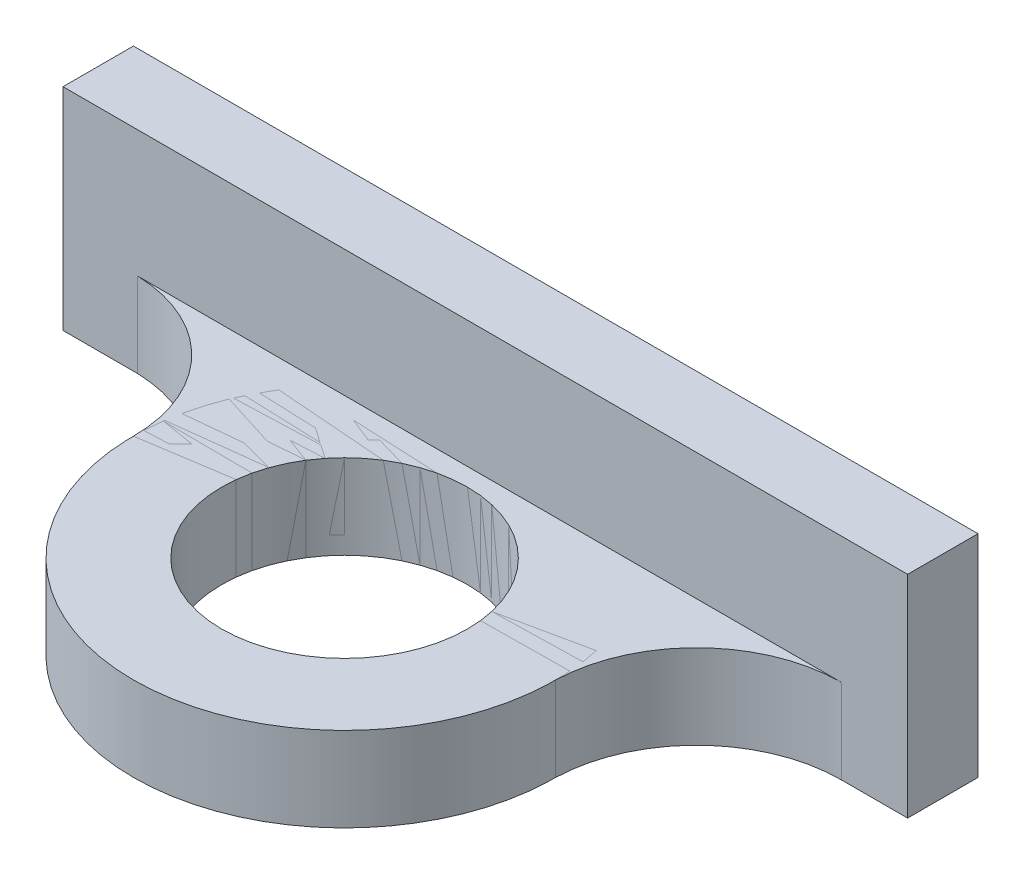
SolidWorks part; units mm, degrees
ref_plane "Front Plane" through (0, 0, 0) normal (0, 0, 1) x (1, 0, 0)
ref_plane "Top Plane" through (0, 0, 0) normal (0, 1, 0) x (1, 0, 0)
ref_plane "Right Plane" through (0, 0, 0) normal (1, 0, 0) x (0, 0, -1)
sketch "Sketch1" plane through (0, 0, 0) normal (0, 1, 0) x (1, 0, 0)
  circle A0 centre (0, 0) radius 17.4625
  circle A1 centre (0, 0) radius 30
  point P0 (0, 0)
  dimension "D2" = 34.925
  dimension "D1" = 60
extrude "Boss-Extrude1" add sketch "Sketch1" along normal blind 12
sketch "Sketch5" plane through (0, 0, 0) normal (0, -1, 0) x (1, 0, 0)
  line L1 (0, -30) -> (60, -30)
  line L4 (60, -30) -> (60, -20)
  line L5 (0, -30) -> (-60, -30)
  line L6 (60, -20) -> (0, -20)
  line L7 (0, -20) -> (-60, -20)
  line L8 (-60, -30) -> (-60, -20)
  point P3 (0, -30)
  point P15 (0, 0)
  dimension "D2" = 60
  dimension "D3" = 10
  dimension "D4" = 60
extrude "Boss-Extrude2" add sketch "Sketch5" against normal blind 30
sketch "Sketch6" plane through (0, 0, 0) normal (0, -1, 0) x (1, 0, 0)
  line L0 (-50.5902, -20) -> (50.5902, -20)
  line L2 (-30, 0) -> (-17.4625, 0)
  line L5 (30, 0) -> (17.4625, 0)
  arc A0 (22.3607, -20) -> (-22.3607, -20) centre (0, 0) ccw construction
  arc A1 (-30, 0) -> (-50.5902, -20) centre (-50.0085, 0) cw
  circle A2 centre (0, 0) radius 17.4625 construction
  arc A3 (50.5902, -20) -> (30, 0) centre (50.5902, 0.5989) cw
  arc A4 (-17.4625, 0) -> (17.4625, 0) centre (0, 0) ccw
  point P19 (0, 0)
  arc M1 (22.3607, -20) -> (-22.3607, -20) centre (0, 0) ccw
  line M2 (-22.3607, -20) -> (-60, -20)
  line M6 (60, -20) -> (22.3607, -20)
  circle M7 centre (0, 0) radius 17.4625
extrude "Boss-Extrude3" add sketch "Sketch6" against normal blind 12 separate body contours L5 L2 L0 M1 M7 | A3 M6 M1 | A1 M1 M2 region at (-27.4343, 0, -10.479) region at (-32.0574, 0, -15.389) region at (32.2393, 0, -15.3151)
ref_point "Point1"
